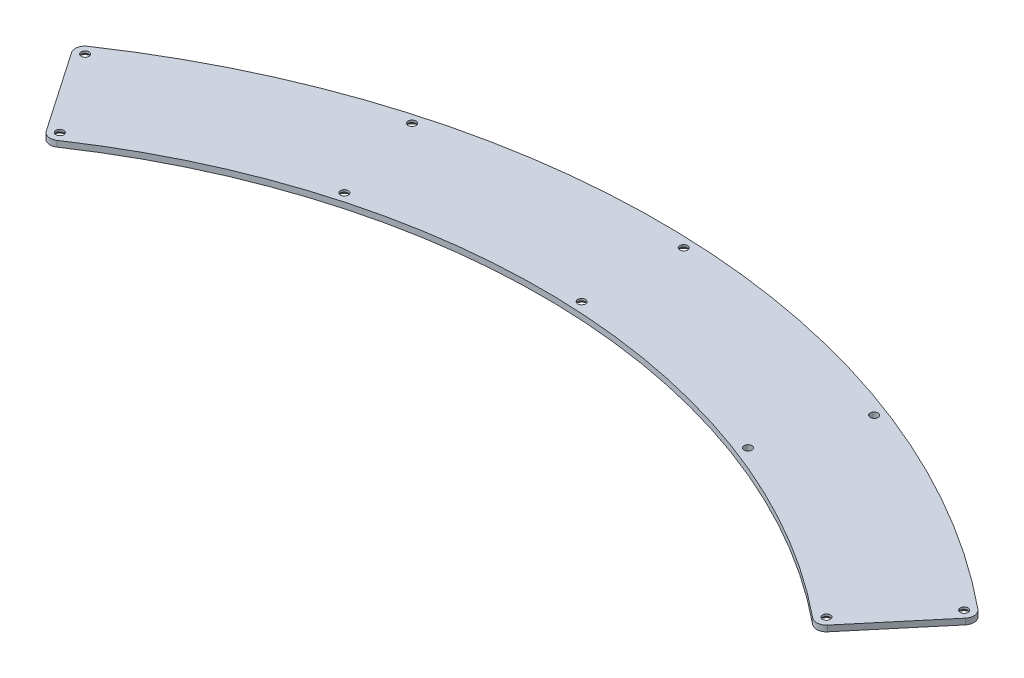
SolidWorks part; units mm, degrees
ref_plane "Спереди" through (0, 0, 0) normal (0, 0, 1) x (1, 0, 0)
ref_plane "Сверху" through (0, 0, 0) normal (0, 1, 0) x (1, 0, 0)
ref_plane "Справа" through (0, 0, 0) normal (1, 0, 0) x (0, 0, -1)
sketch "Эскиз1" plane through (0, 0, 0) normal (0, 1, 0) x (1, 0, 0)
  line L0 (-218.5478, 260.4551) -> (-257.115, 306.4178) construction
  line L1 (0, 0) -> (0, 259.5027) construction
  line L2 (218.5478, 260.4551) -> (257.115, 306.4178) construction
  line L3 (-218.5478, 260.4551) -> (-257.115, 306.4178)
  line L4 (257.115, 306.4178) -> (218.5478, 260.4551)
  line L10 (0, 344.4859) -> (0, 245.0378) construction
  line L11 (0, 0) -> (-257.115, 306.4178) construction
  line L12 (0, 0) -> (257.115, 306.4178) construction
  arc A0 (257.115, 306.4178) -> (-257.115, 306.4178) centre (0, 0) ccw construction
  arc A1 (257.115, 306.4178) -> (-257.115, 306.4178) centre (0, 0) ccw
  arc A2 (218.5478, 260.4551) -> (-218.5478, 260.4551) centre (0, 0) ccw
  dimension "D1" = 340
  dimension "D2" = 400
  dimension "D4" = 40
  dimension "D5" = 40
sheet metal parameters "Листовой металл1" thickness 3 parameters "D1"=1.2, "Толщина"=3
base flange "Базовая кромка1" sketch "Эскиз1" thickness 3 reverse thickness direction no parameters "D1"=1.2
sketch "Эскиз2" plane through (0, 0, 0) normal (0, 1, 0) x (1, 0, 0)
  line L0 (-185.8708, 267.0034) -> (-232.6689, 335.2079)
  line L1 (-225.6582, 324.158) -> (-197.089, 283.1182) construction
  line L2 (-232.6689, 335.2079) -> (-262.0244, 311.2157)
  line L3 (-262.0244, 311.2157) -> (-219.7739, 254.7205)
  line L4 (-219.7739, 254.7205) -> (-185.8708, 267.0034)
extrude "Вырез-Вытянуть1" cut sketch "Эскиз2" against normal blind 10 normal cut yes
fillet "Скругление1" radius 5 2 edges at (-194.1716, -1.5, -279.1011) (-228.1184, -1.5, -328.5757)
fillet "Скругление2" radius 5 2 edges at (218.5478, -1.5, -260.4551) (257.115, -1.5, -306.4178)
sketch "Эскиз3" plane through (0, 0, 0) normal (0, 1, 0) x (1, 0, 0)
  circle A0 centre (-221.1645, 327.2786) radius 2
  circle A1 centre (-192.8752, 286.0492) radius 2
  circle A2 centre (217.9082, 267.4715) radius 2
  circle A3 centre (250.0505, 305.7773) radius 2
  dimension "D1" = 4
  dimension "D2" = 4
  dimension "D3" = 4
  dimension "D4" = 4
extrude "Вырез-Вытянуть2" cut sketch "Эскиз3" against normal blind 10 normal cut yes
sketch "Эскиз5" plane through (0, 0, 0) normal (0, 1, 0) x (1, 0, 0)
  circle A0 centre (15.5203, 344.6507) radius 2
  circle A1 centre (17.7697, 394.6001) radius 2
  circle A2 centre (-106.9048, 380.2583) radius 2
  circle A3 centre (-93.3725, 332.1243) radius 2
  dimension "D1" = 4
  dimension "D2" = 4
extrude "Вырез-Вытянуть4" cut sketch "Эскиз5" against normal blind 10 normal cut yes
chamfer "Фаска1" distance 1.9 angle 45 8 edges at (-221.1645, -3, -325.2786) (-192.8752, -3, -284.0492) (-93.3725, -3, -330.1243) (-106.9048, -3, -378.2583) (15.5203, -3, -342.6507) (17.7697, -3, -392.6001) (217.9082, -3, -265.4715) (250.0505, -3, -303.7773)
sketch "Эскиз6" plane through (0, 0, 0) normal (0, 1, 0) x (1, 0, 0)
  circle A0 centre (140.6504, 369.1104) radius 2
  circle A1 centre (122.8466, 322.3875) radius 2
  dimension "D1" = 4
  dimension "D2" = 4
extrude "Вырез-Вытянуть5" cut sketch "Эскиз6" against normal blind 10 normal cut yes
flat pattern "Развертка1" [suppressed]
sketch "Сгиб-Линии1" plane through (0, 0, 0) normal (0, 1, 0) x (1, 0, 0)
sketch3d "Граничная рамка1" [suppressed]
  line L0 (-105.7369, 160.0484, 0) -> (154.0999, 114.2321, 0) construction
  line L1 (-89.9793, 249.4139, 0) -> (169.8575, 203.5977, 0) construction
  line L2 (-105.7369, 160.0484, 0) -> (-89.9793, 249.4139, 0) construction
  line L3 (154.0999, 114.2321, 0) -> (169.8575, 203.5977, 0) construction
